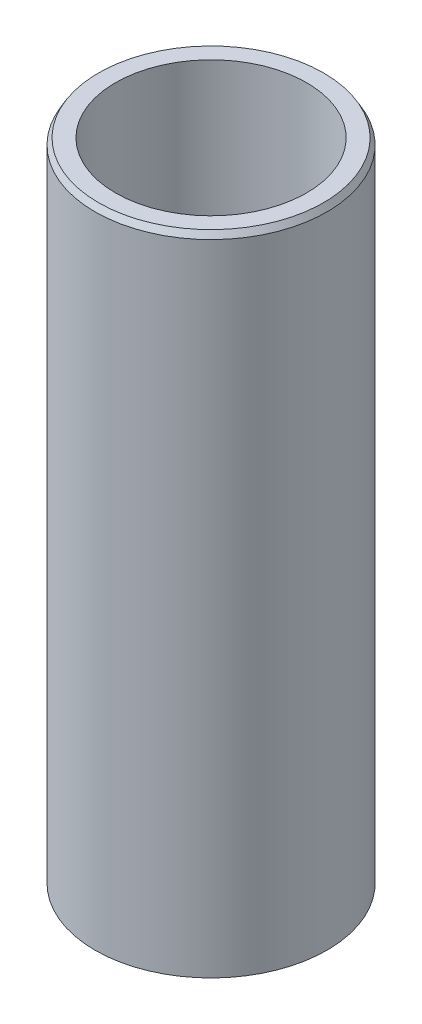
SolidWorks part; units mm, degrees
ref_plane "Front Plane" through (0, 0, 0) normal (0, 0, 1) x (1, 0, 0)
ref_plane "Top Plane" through (0, 0, 0) normal (0, 1, 0) x (1, 0, 0)
ref_plane "Right Plane" through (0, 0, 0) normal (1, 0, 0) x (0, 0, -1)
sketch "Sketch1" plane through (0, 0, 0) normal (0, 1, 0) x (1, 0, 0)
  circle A0 centre (0, 0) radius 52.5
  dimension "SHAFT_OD" = 105
extrude "Boss-Extrude1" add sketch "Sketch1" along normal blind 293.7497
sketch "Sketch2" plane through (0, 0, 0) normal (0, 1, 0) x (1, 0, 0)
  circle A0 centre (0, 0) radius 43.245
  dimension "BORE_D" = 86.4901
extrude "Cut-Extrude1" cut sketch "Sketch2" along normal through all
chamfer "Chamfer1" distance 2.7758 angle 30 2 edges at (0, 293.7497, 52.5) (0, 0, 52.5) first distance on face at (0, 293.7497, 52.5) first distance on face at (0, 0, 43.245)
